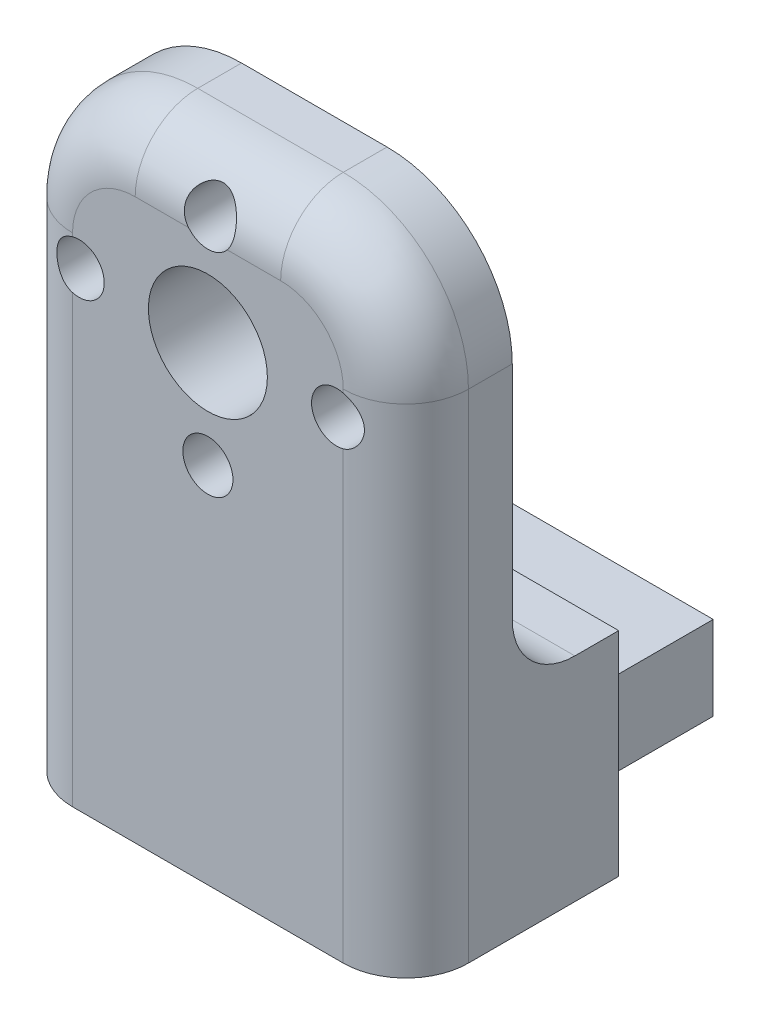
SolidWorks part; units mm, degrees
ref_plane "Front Plane" through (0, 0, 0) normal (0, 0, 1) x (1, 0, 0)
ref_plane "Top Plane" through (0, 0, 0) normal (0, 1, 0) x (1, 0, 0)
ref_plane "Right Plane" through (0, 0, 0) normal (1, 0, 0) x (0, 0, -1)
sketch "Sketch1" plane through (0, 0, 0) normal (0, 1, 0) x (1, 0, 0)
  line L1 (15.81, 8.5) -> (-15.81, 8.5)
  line L2 (15.81, 8.5) -> (15.81, -8.5)
  line L3 (15.81, -8.5) -> (-15.81, -8.5)
  line L4 (-15.81, 8.5) -> (-15.81, -8.5)
  line L5 (15.81, 8.5) -> (-15.81, -8.5) construction
  line L6 (15.81, -8.5) -> (-15.81, 8.5) construction
  point P0 (0, 0)
  dimension "D1" = 31.62
extrude "Boss-Extrude1" add sketch "Sketch1" along normal blind 17
sketch "Sketch2" plane through (0, 0, -8.5) normal (0, 0, -1) x (-1, 0, 0)
  line L0 (-15.81, 0) -> (15.81, 0) construction
  line L1 (-13.66, 11.85) -> (13.66, 11.85)
  line L2 (-13.66, 11.85) -> (-13.66, 5.15)
  line L3 (-13.66, 5.15) -> (13.66, 5.15)
  line L4 (13.66, 11.85) -> (13.66, 5.15)
  line L5 (-13.66, 11.85) -> (13.66, 5.15) construction
  line L6 (-13.66, 5.15) -> (13.66, 11.85) construction
  line L7 (0, 11.85) -> (0, 17)
  line L8 (-15.81, 17) -> (15.81, 17) construction
  line L9 (0, 5.15) -> (0, 0)
  point P0 (0, 8.5)
  point P7 (0, 0)
extrude "Boss-Extrude2" add sketch "Sketch2" along normal blind 9.7 contours L4 L1 L2 L3 region at (0, 8.5, -8.5)
sketch "Sketch3" plane through (0, 17, 0) normal (0, 1, 0) x (1, 0, 0)
  line L0 (15.81, -8.5) -> (15.81, 8.5) construction
  line L1 (15.81, 0) -> (-15.81, 0)
  line L2 (15.81, 0) -> (15.81, -8.5)
  line L3 (15.81, -8.5) -> (-15.81, -8.5)
  line L4 (-15.81, 0) -> (-15.81, -8.5)
extrude "Boss-Extrude3" add sketch "Sketch3" along normal blind 32.7
sketch "Sketch4" plane through (0, 0, 8.5) normal (0, 0, 1) x (1, 0, 0)
  line L0 (0, 0) -> (0, 37.5)
  line L1 (-15.81, 0) -> (15.81, 0) construction
  line L2 (-4.75, 37.5) -> (-15.81, 37.5)
  line L5 (0, 42.25) -> (0, 49.7)
  line L7 (0, 37.5) -> (0, 25.3)
  line L8 (-15.81, 49.7) -> (-15.81, 0) construction
  line L9 (4.75, 37.5) -> (15.81, 37.5)
  line L10 (15.81, 49.7) -> (15.81, 0) construction
  line L11 (-15.81, 49.7) -> (15.81, 49.7) construction
  circle A0 centre (0, 37.5) radius 4.75
  circle A1 centre (-10.28, 37.5) radius 2
  circle A2 centre (10.28, 37.5) radius 2
  circle A3 centre (0, 45.975) radius 2
  circle A4 centre (0, 29.025) radius 2
  point P24 (0, 0)
  point P25 (0, 45.975)
extrude "Cut-Extrude1" cut sketch "Sketch4" against normal blind 43.7 contours A0 | A4 L7 | A4 L7 | A1 | A2 | A3 region at (-0.8488, 29.025, 8.5) region at (-3.2638, 34.2362, 8.5) region at (0.8488, 29.025, 8.5)
fillet "Fillet1" radius 10 2 edges at (-15.81, 49.7, 4.25) (15.81, 49.7, 4.25)
fillet "Fillet2" radius 5 1 edges at (0, 17, 0)
fillet "Fillet3" radius 5 5 edges at (-15.81, 19.85, 8.5) (-12.8811, 46.7711, 8.5) (0, 49.7, 8.5) (12.8811, 46.7711, 8.5) (15.81, 19.85, 8.5)
